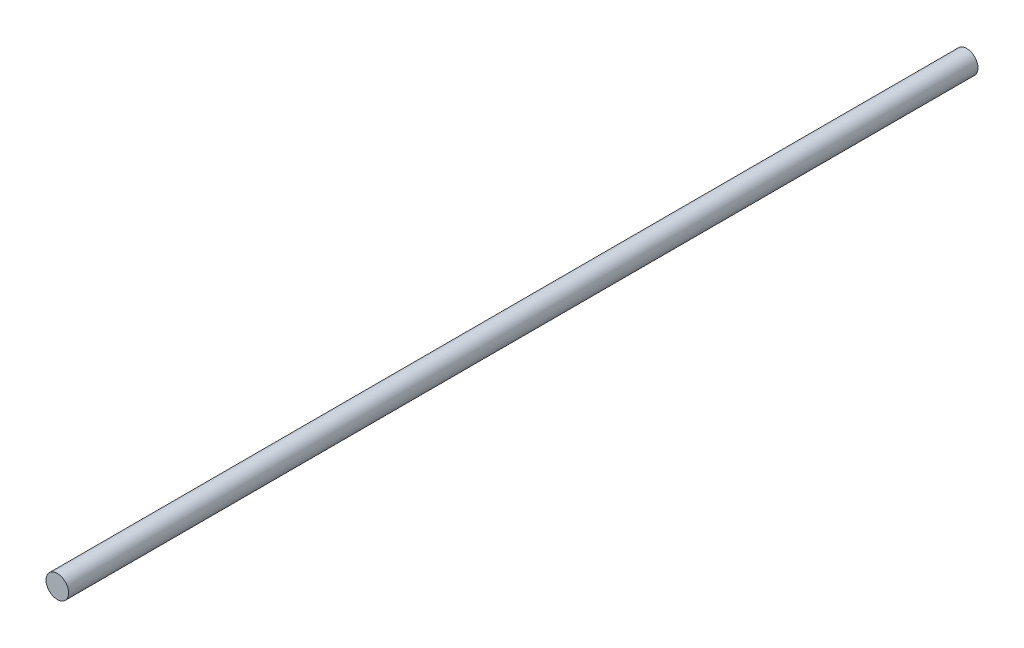
SolidWorks part; units mm, degrees
ref_plane "Front Plane" through (0, 0, 0) normal (0, 0, 1) x (1, 0, 0)
ref_plane "Top Plane" through (0, 0, 0) normal (0, 1, 0) x (1, 0, 0)
ref_plane "Right Plane" through (0, 0, 0) normal (1, 0, 0) x (0, 0, -1)
sketch "Sketch1" plane through (0, 0, 0) normal (0, 0, 1) x (1, 0, 0)
  circle A0 centre (0, 0) radius 4.5
  dimension "D1" = 9
extrude "Boss-Extrude1" add sketch "Sketch1" along normal blind 361.8
ref_axis "Axis1" through (0, 0, 361.8) along (0, 0, -1)
